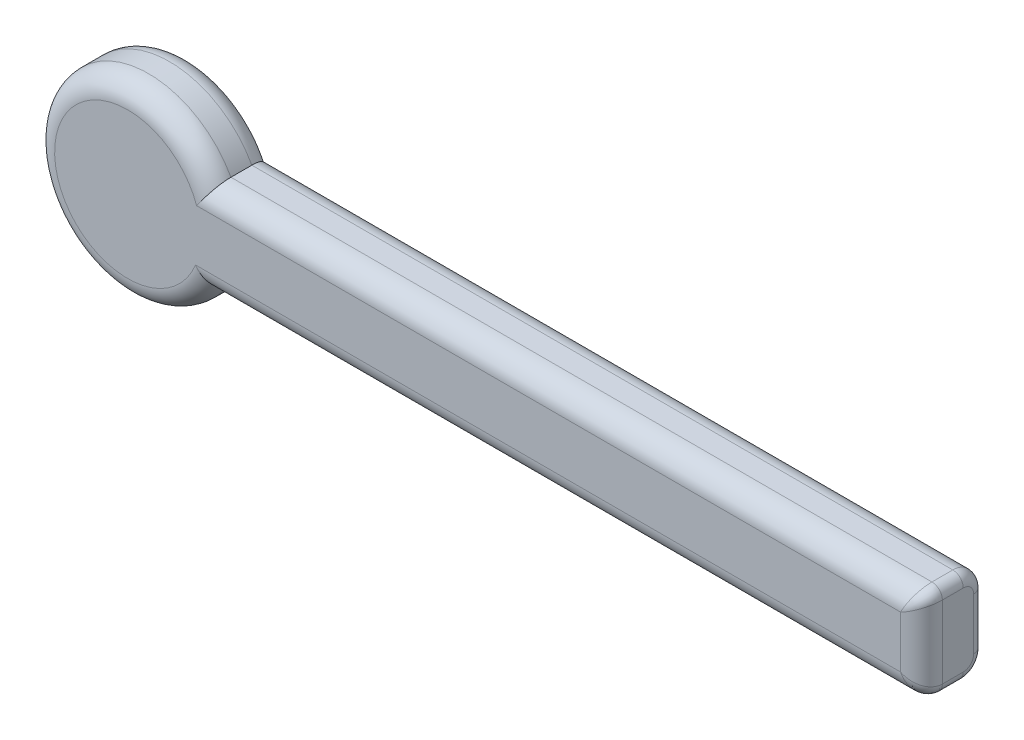
SolidWorks part; units mm, degrees
ref_plane "Ön Düzlem" through (0, 0, 0) normal (0, 0, 1) x (1, 0, 0)
ref_plane "Üst Düzlem" through (0, 0, 0) normal (0, 1, 0) x (1, 0, 0)
ref_plane "Sağ Düzlem" through (0, 0, 0) normal (1, 0, 0) x (0, 0, -1)
sketch "Çizim1" plane through (0, 0, 0) normal (0, 0, 1) x (1, 0, 0)
  circle A0 centre (0, 0) radius 45
  dimension "D1" = 90
extrude "Yükseklik-Ekstrüzyon1" add sketch "Çizim1" along normal blind 30
ref_plane "Düzlem1" through (0, 0, 25) normal (0, 0, 1) x (1, 0, 0)
sketch "Çizim12" plane through (0, 0, 30) normal (0, 0, 1) x (1, 0, 0)
  line L0 (30, 21.7273) -> (30, -23.1056)
  line L1 (30, 21.7273) -> (380, 21.7273)
  line L2 (30, -23.1056) -> (380, -23.1056)
  line L3 (380, 21.7273) -> (380, -23.1056)
  circle A1 centre (0, 0) radius 45 construction
  dimension "D1" = 350
  dimension "D2" = 30
extrude "Yükseklik-Ekstrüzyon4" add sketch "Çizim12" against normal blind 30
sketch "Çizim15" plane through (0, 0, 0) normal (0, 0, -1) x (-1, 0, 0)
  circle A0 centre (0, 0) radius 2.5
  dimension "D1" = 5
extrude "Kes-Ekstrüzyon6" cut sketch "Çizim15" against normal blind 20
ref_plane "Düzlem2" through (305, 0, 0) normal (1, 0, 0) x (0, 0, -1)
sketch "Çizim16" plane through (0, 0, 0) normal (0, 0, -1) x (-1, 0, 0)
  line L1 (-364.8847, -10) -> (-324.8847, -10)
  line L2 (-364.8847, -10) -> (-364.8847, 10)
  line L3 (-364.8847, 10) -> (-324.8847, 10)
  line L4 (-324.8847, -10) -> (-324.8847, 10)
  line L5 (-364.8847, -10) -> (-324.8847, 10) construction
  line L6 (-364.8847, 10) -> (-324.8847, -10) construction
  point P0 (-344.8847, 0)
  dimension "D1" = 40
  dimension "D2" = 20
extrude "Kes-Ekstrüzyon7" cut sketch "Çizim16" against normal blind 22
fillet "Radyus1" radius 10 7 edges at (380, -0.6892, 30) (209.3076, -23.1056, 30) (209.7036, 21.7273, 30) (-44.993, 0.7948, 30) (-44.993, 0.7948, 0) (209.3076, -23.1056, 0) (209.7036, 21.7273, 0)
fillet "Radyus2" radius 5 7 edges at (377.0711, -20.1767, 27.0711) (380, -23.1056, 15) (380, -20.1767, 2.9289) (377.0711, 18.7984, 27.0711) (380, 21.7273, 15) (380, 18.7984, 2.9289) (380, -0.6892, 0)
